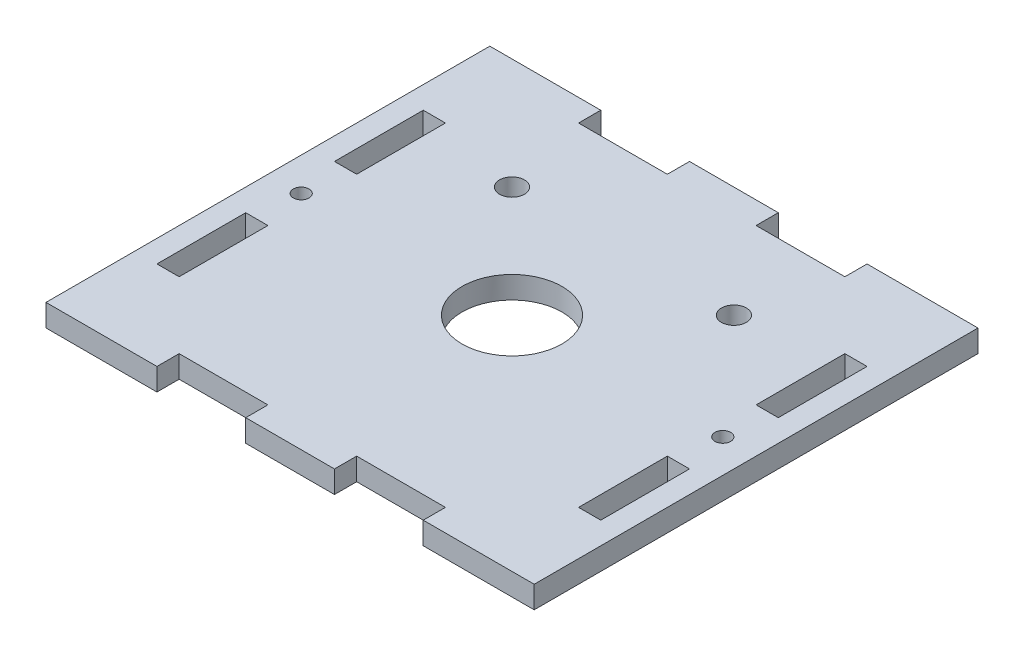
SolidWorks part; units mm, degrees
ref_plane "Front Plane" through (0, 0, 0) normal (0, 0, 1) x (1, 0, 0)
ref_plane "Top Plane" through (0, 0, 0) normal (0, 1, 0) x (1, 0, 0)
ref_plane "Right Plane" through (0, 0, 0) normal (1, 0, 0) x (0, 0, -1)
sketch "Sketch1" plane through (0, 0, 0) normal (0, 1, 0) x (1, 0, 0)
  line L1 (0, 0) -> (139.7, 0)
  line L2 (0, 0) -> (0, 127)
  line L3 (0, 127) -> (139.7, 127)
  line L4 (139.7, 0) -> (139.7, 127)
  dimension "D1" = 127
  dimension "D2" = 139.7
extrude "Boss-Extrude1" add sketch "Sketch1" along normal blind 6.35
sketch "Sketch13" plane through (0, 6.35, 0) normal (0, 1, 0) x (1, 0, 0)
  line L0 (0, 0) -> (139.7, 0) construction
  line L1 (31.75, 0) -> (57.15, 0)
  line L2 (31.75, 0) -> (31.75, 6.35)
  line L3 (31.75, 6.35) -> (57.15, 6.35)
  line L4 (57.15, 0) -> (57.15, 6.35)
  line L5 (82.55, 6.35) -> (107.95, 6.35)
  line L6 (107.95, 0) -> (107.95, 6.35)
  line L7 (82.55, 0) -> (107.95, 0)
  line L8 (82.55, 0) -> (82.55, 6.35)
  line L17 (31.75, 6.35) -> (82.55, 6.35) construction
  line L18 (0, 127) -> (0, 0) construction
  dimension "D1" = 25.4
  dimension "D2" = 6.35
  dimension "D4" = 50.8
  dimension "D5" = 31.75
  dimension "D3" = 2
extrude "Cut-Extrude6" cut sketch "Sketch13" against normal blind 6.35
pattern_linear "LPattern7" count 2 spacing 120.65 along (0, 0, -1) of "Cut-Extrude6"
sketch "Sketch14" plane through (0, 6.35, 0) normal (0, 1, 0) x (1, 0, 0)
  line L0 (0, 127) -> (0, 0) construction
  line L1 (6.35, 25.4) -> (12.7, 25.4)
  line L2 (6.35, 25.4) -> (6.35, 50.8)
  line L3 (6.35, 50.8) -> (12.7, 50.8)
  line L4 (12.7, 25.4) -> (12.7, 50.8)
  line L5 (0, 0) -> (31.75, 0) construction
  line L6 (127, 50.8) -> (133.35, 50.8)
  line L7 (127, 25.4) -> (127, 50.8)
  line L8 (133.35, 25.4) -> (133.35, 50.8)
  line L9 (127, 25.4) -> (133.35, 25.4)
  line L10 (127, 101.6) -> (133.35, 101.6)
  line L11 (127, 76.2) -> (127, 101.6)
  line L12 (133.35, 76.2) -> (133.35, 101.6)
  line L13 (127, 76.2) -> (133.35, 76.2)
  line L14 (6.35, 101.6) -> (12.7, 101.6)
  line L15 (6.35, 76.2) -> (6.35, 101.6)
  line L16 (12.7, 76.2) -> (12.7, 101.6)
  line L17 (6.35, 76.2) -> (12.7, 76.2)
  dimension "D1" = 25.4
  dimension "D2" = 6.35
  dimension "D3" = 6.35
  dimension "D4" = 25.4
  dimension "D5" = 2
  dimension "D6" = 2
extrude "Cut-Extrude7" cut sketch "Sketch14" against normal blind 6.35
hole_wizard "#8 Clearance Hole1" positions "Sketch16" profile "Sketch15" hole size "#8" standard "ANSI Inch"
sketch "Sketch16" plane through (0, 6.35, 0) normal (0, 1, 0) x (1, 0, 0)
  line L0 (12.7, 50.8) -> (6.35, 50.8) construction
  line L1 (6.35, 50.8) -> (6.35, 25.4) construction
  line L2 (133.35, 50.8) -> (127, 50.8) construction
  line L3 (127, 50.8) -> (127, 25.4) construction
  point P0 (9.525, 63.5)
  point P3 (9.525, 50.8)
  point P8 (130.175, 63.5)
  dimension "D1" = 12.7
  dimension "D2" = 3.175
  dimension "D3" = 12.7
  dimension "D4" = 3.175
sketch "Sketch15" plane through (9.525, 6.35, -63.5) normal (1, 0, 0) x (0, 0, 1)
  line L0 (0, 0) -> (0, 11.5107)
  line L1 (0, 11.5107) -> (2.2479, 10.16)
  line L2 (2.2479, 10.16) -> (2.2479, 0)
  line L5 (2.2479, 0) -> (0, 0)
  line L10 (0, 11.5107) -> (-2.2479, 10.16) construction
  line L11 (0, -6.35) -> (0, 107.95) construction
  dimension "Hole Dia." = 4.4958
  dimension "Hole Depth" = 10.16
  dimension "Drill Angle" = 118
sketch "Sketch18" plane through (0, 6.35, 0) normal (0, 1, 0) x (1, 0, 0)
  line L0 (0, 127) -> (0, 0) construction
  circle A0 centre (69.85, 63.5) radius 14.2875
  point P4 (0, 63.5)
  dimension "D1" = 28.575
  dimension "D2" = 69.85
extrude "Cut-Extrude9" cut sketch "Sketch18" against normal blind 7.62
sketch "Sketch19" plane through (0, 6.35, 0) normal (0, 1, 0) x (1, 0, 0)
  line L0 (31.75, 127) -> (31.75, 120.65) construction
  line L1 (107.95, 120.65) -> (107.95, 127) construction
  line L2 (31.75, 120.65) -> (57.15, 120.65) construction
  line L3 (82.55, 120.65) -> (107.95, 120.65) construction
  circle A0 centre (38.1, 95.25) radius 3.5719
  circle A1 centre (101.6, 95.25) radius 3.5719
  dimension "D1" = 7.1437
  dimension "D2" = 7.1437
  dimension "D3" = 6.35
  dimension "D5" = 25.4
  dimension "D6" = 25.4
  dimension "D4" = 6.35
extrude "Cut-Extrude10" cut sketch "Sketch19" against normal blind 7.62
equation "\"THICK\"= .25"
